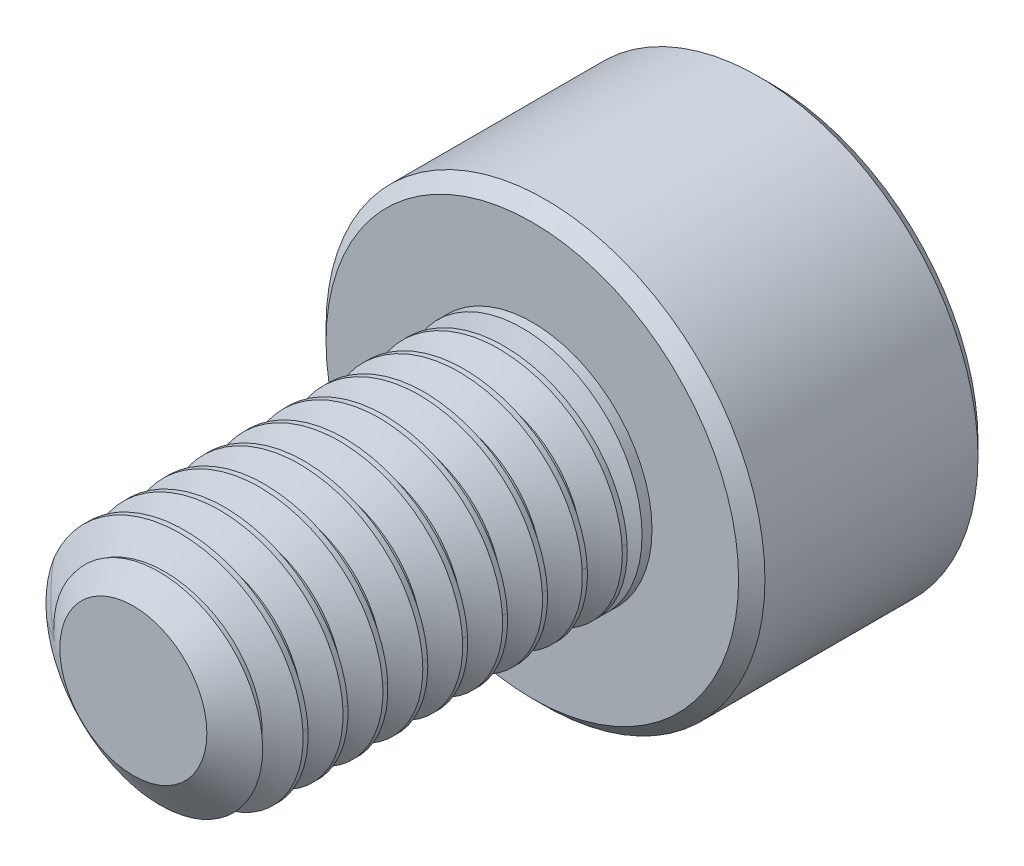
SolidWorks part; units mm, degrees
ref_plane "Front Plane" through (0, 0, 0) normal (0, 0, 1) x (1, 0, 0)
ref_plane "Top Plane" through (0, 0, 0) normal (0, 1, 0) x (1, 0, 0)
ref_plane "Right Plane" through (0, 0, 0) normal (1, 0, 0) x (0, 0, -1)
sketch "Sketch1" plane through (0, 0, 0) normal (0, 0, 1) x (1, 0, 0)
  circle A0 centre (0, 0) radius 1.5
  dimension "OD" = 3
extrude "Extrude1" add sketch "Sketch1" against normal blind 5
sketch "Sketch2" plane through (0, 0, 0) normal (0, 0, 1) x (1, 0, 0)
  circle A0 centre (0, 0) radius 1.5 construction
  circle A1 centre (0, 0) radius 1.5
curve "Helix/Spiral1" pitch 0.5 height 5.5 radius 1.5 centre (0, 0, 0) axis (0, 0, -1) start towards (0, 1, 0) parameters "pitch"=0.5
sketch "Sketch3" plane through (0, 0, 0) normal (1, 0, 0) x (0, 0, -1)
  line L0 (-0.4375, 1.5) -> (-0.25, 1.1752)
  line L1 (-0.25, 1.1752) -> (-0.1875, 1.1752)
  line L2 (-0.1875, 1.1752) -> (0, 1.5)
  line L3 (-0.4375, 1.5) -> (0, 1.5)
  line L4 (-0.2188, 1.5) -> (-0.2188, 1.1752) construction
  line L5 (-0.3438, 1.3376) -> (-0.0938, 1.3376) construction
  line L6 (0, 1.5) -> (0, -1.5) construction
  line L7 (0, -1.5) -> (5, -1.5) construction
  point P11 (2.25, -1.5)
  dimension "D1" = 0.0625
  dimension "D2" = 0.25
  dimension "D3" = 60
  dimension "D4" = 2.25
sweep "Cut-Sweep1" cut profiles "Sketch3" path "Helix/Spiral1" align with end faces yes
sketch "Sketch4" plane through (0, 0, 0) normal (1, 0, 0) x (0, 0, -1)
  line L0 (0.4053, 1.5) -> (0, 0.9212)
  line L1 (0, 0.9212) -> (0, 1.5)
  line L2 (0.4053, 1.5) -> (0, 1.5)
  line L3 (-0.4375, 1.5) -> (0, 1.5) construction
  line L4 (0, 0) -> (7.0209, 0) construction
  dimension "D1" = 55
  dimension "D2" = 0.254
revolve "Cut-Revolve1" cut sketch "Sketch4" angle 360 about L4
sketch "Sketch5" plane through (0, 0, 0) normal (1, 0, 0) x (0, 0, -1)
  line L0 (5, -1.1822) -> (5, 1.0703) construction
  line L1 (5, 1.5) -> (0.1202, 1.5)
  line L2 (5, 1.5) -> (5, 0)
  line L3 (5, 0) -> (0, 0)
  line L4 (0, 1.1698) -> (0, 0)
  line L5 (0.1202, 1.5) -> (0, 1.1698)
  line L6 (0, 0) -> (9.9695, 0) construction
  point P3 (0, 1.5)
  point P10 (0, 1.5)
  dimension "D1" = 0.3302
  dimension "D3" = 20
  dimension "Thread Min" = 0
revolve "partially thread" [suppressed] add sketch "Sketch5" angle 360 about L6
sketch "Sketch6" plane through (0, 0, -5) normal (0, 0, -1) x (-1, 0, 0)
  circle A0 centre (0, 0) radius 2.75
  dimension "head dia" = 5.5
extrude "Extrude2" add sketch "Sketch6" along normal blind 3
sketch "Sketch7" plane through (0, 0, -8) normal (0, 0, -1) x (-1, 0, 0)
  line L1 (0, 1.4434) -> (-1.25, 0.7217)
  line L2 (-1.25, 0.7217) -> (-1.25, -0.7217)
  line L3 (-1.25, -0.7217) -> (0, -1.4434)
  line L4 (0, -1.4434) -> (1.25, -0.7217)
  line L5 (1.25, -0.7217) -> (1.25, 0.7217)
  line L6 (1.25, 0.7217) -> (0, 1.4434)
  circle A0 centre (0, 0) radius 1.25 construction
  dimension "hex dia" = 2.5
extrude "Cut-Extrude1" cut sketch "Sketch7" against normal blind 1.875
sketch "Sketch8" plane through (0, 0, -8) normal (0, 0, -1) x (-1, 0, 0)
  circle A0 centre (0, 0) radius 1.4434
extrude "Cut-Extrude2" cut sketch "Sketch8" against normal through all draft 45
chamfer "Chamfer1" distance 0.165 angle 45 2 edges at (-2.75, 0, -8) (-2.75, 0, -5)
sketch "Sketch9" plane through (0, 0, 0) normal (1, 0, 0) x (0, 0, -1)
  line L0 (0, 1.5) -> (0, -1.5) construction
  line L1 (2.75, 1.5) -> (2.75, -1.5) construction
  dimension "D1" = 2.75
sketch "Sketch10" plane through (0, 0, 0) normal (1, 0, 0) x (0, 0, -1)
  line L0 (5, 1.5) -> (5, 0)
  line L1 (5, 1.5) -> (4.875, 1.5)
  line L2 (4.875, 1.5) -> (4.2537, 0)
  line L3 (5, 0) -> (4.2537, 0)
  line L4 (5, 2.585) -> (5, -2.585) construction
  dimension "D1" = 22.5
  dimension "D2" = 0.125
revolve "Revolve1" add sketch "Sketch10" angle 360 about L3
equation "\"D3@Helix/Spiral1\" = \"screw length@Extrude1\"+\"pitch@Helix/Spiral1\""
equation "\"D1@Sketch3\" = \"pitch@Helix/Spiral1\"*.125"
equation "\"D2@Sketch3\" = \"pitch@Helix/Spiral1\"*.5"
equation "\"D1@Cut-Extrude1\" = \"hex dia@Sketch7\"*.75"
equation "\"D1@Chamfer1\" = \"head dia@Sketch6\"*.03"
equation "\"D1@Sketch9\" = \"pitch@Helix/Spiral1\"*5.5"
equation "\"D2@Sketch10\" = \"pitch@Helix/Spiral1\"*.25"
equation "\"D4@Sketch3\" = \"pitch@Helix/Spiral1\"*4.50"
